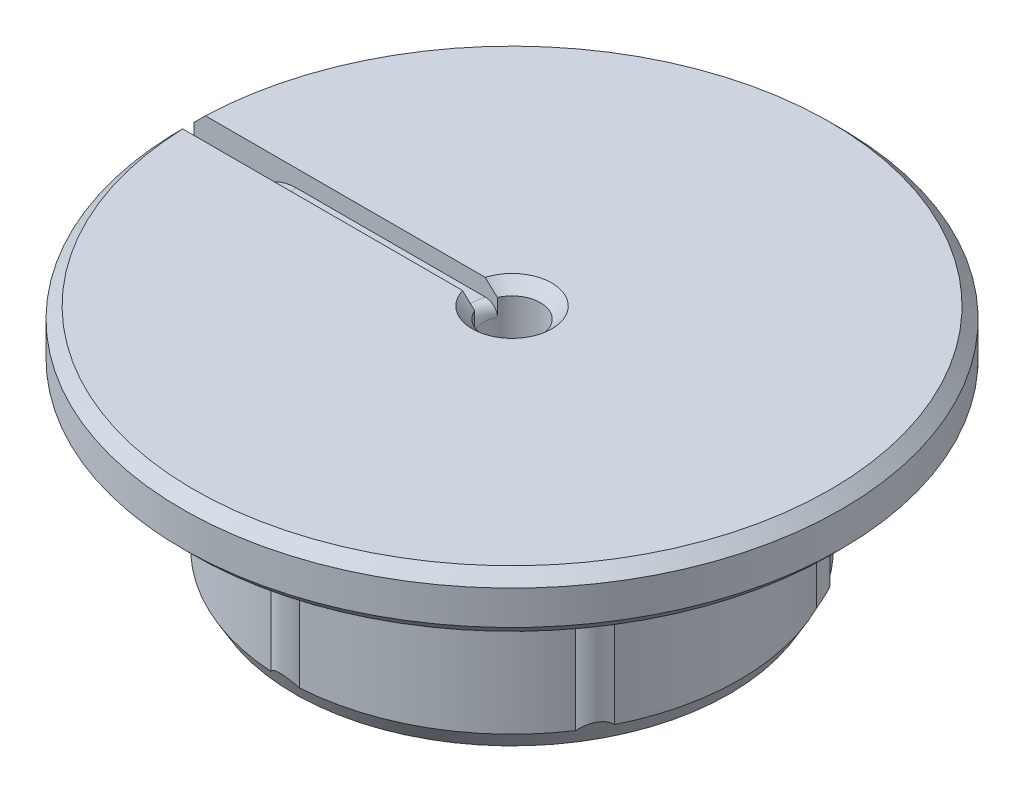
SolidWorks part; units mm, degrees
ref_plane "Front Plane" through (0, 0, 0) normal (0, 0, 1) x (1, 0, 0)
ref_plane "Top Plane" through (0, 0, 0) normal (0, 1, 0) x (1, 0, 0)
ref_plane "Right Plane" through (0, 0, 0) normal (1, 0, 0) x (0, 0, -1)
sketch "Sketch1" plane through (0, 0, 0) normal (0, 0, 1) x (1, 0, 0)
  line L0 (0, 0) -> (0, 30415.8317) construction
  line L1 (0, 0) -> (20, 0)
  line L2 (20, 0) -> (20, 15)
  line L3 (20, 15) -> (29, 15)
  line L4 (29, 15) -> (29, 20)
  line L5 (29, 20) -> (2.5, 20)
  line L6 (2.5, 20) -> (2.5, 10)
  line L7 (2.5, 10) -> (0, 10)
  line L9 (0, 10) -> (0, 0)
  dimension "D1" = 40
  dimension "D2" = 5
  dimension "D3" = 15
  dimension "D4" = 5
  dimension "D5" = 10
  dimension "D6" = 9
revolve "Revolve1" add sketch "Sketch1" angle 360 about L0
sketch "Sketch2" plane through (0, 0, 0) normal (0, -1, 0) x (1, 0, 0)
  arc A0 (-1.25, 19.9609) -> (1.25, 19.9609) centre (0, 18.4888) cw
  circle A1 centre (0, 0) radius 20 construction
  circle A2 centre (0, 0) radius 20 construction
  arc A3 (-1.25, 19.9609) -> (-16.6616, 11.063) centre (0, 0) ccw
  arc A4 (16.6616, 11.063) -> (17.9116, 8.8979) centre (16.0117, 9.2444) cw
  arc A5 (17.9116, -8.8979) -> (16.6616, -11.063) centre (16.0117, -9.2444) cw
  arc A6 (1.25, -19.9609) -> (-1.25, -19.9609) centre (0, -18.4888) cw
  arc A7 (-16.6616, -11.063) -> (-17.9116, -8.8979) centre (-16.0117, -9.2444) cw
  arc A8 (-17.9116, 8.8979) -> (-16.6616, 11.063) centre (-16.0117, 9.2444) cw
  arc A9 (-17.9116, 8.8979) -> (-17.9116, -8.8979) centre (0, 0) ccw
  arc A10 (-16.6616, -11.063) -> (-1.25, -19.9609) centre (0, 0) ccw
  arc A11 (1.25, -19.9609) -> (16.6616, -11.063) centre (0, 0) ccw
  arc A12 (17.9116, -8.8979) -> (17.9116, 8.8979) centre (0, 0) ccw
  arc A13 (16.6616, 11.063) -> (1.25, 19.9609) centre (0, 0) ccw
  point P27 (0, 0)
  dimension "D2" = 20.42
  dimension "D1" = 2.5
  dimension "D3" = 6
extrude "Boss-Extrude1" add sketch "Sketch2" against normal offset from surface (10 mm away) 5 up to face at (0, 15, -29)
sketch "Sketch3" plane through (0, 0, 0) normal (0, 0, 1) x (1, 0, 0)
  line L0 (-21, 3.2321) -> (-18.5566, -1)
  line L1 (-18.5566, -1) -> (-21, -1)
  line L2 (-21, -1) -> (-21, 3.2321)
  line L3 (-20, 0) -> (-17.9116, 0) construction
  dimension "D1" = 0.75
  dimension "D2" = 1
  dimension "D3" = 1
  dimension "D4" = 60
ref_axis "Axis1" through (0, 29.3369, 0) along (0, -1, 0)
revolve "Cut-Revolve1" cut sketch "Sketch3" angle 360 about axis through (0, 29.3369, 0) along (0, -1, 0)
chamfer "Chamfer1" distance 1 angle 45 3 edges at (0, 20, -2.5) (0, 15, -29) (0, 20, -29)
sketch "Sketch4" plane through (0, 0, 0) normal (0, -1, 0) x (1, 0, 0)
  line L0 (-23.93, 1) -> (-100, 1)
  line L1 (-100, -1) -> (-23.93, -1)
  line L2 (-100, 1) -> (-100, -1)
  line L3 (-23.93, -1) -> (-23.93, 1)
  point P5 (-100, 0)
  dimension "D1" = 2
  dimension "D2" = 100
  dimension "D3" = 23.93
extrude "Cut-Extrude1" cut sketch "Sketch4" against normal through all
sketch "Sketch5" plane through (-23.93, 0, 0) normal (-1, 0, 0) x (0, 0, 1)
  line L0 (1, 16) -> (1, 19) construction
  line L1 (-1, 20) -> (1, 20)
  line L2 (-1, 20) -> (-1, 18.5)
  line L3 (-1, 18.5) -> (1, 18.5)
  line L4 (1, 20) -> (1, 18.5)
  line L5 (1, 20) -> (1, 15) construction
  dimension "D1" = 1.5
extrude "Cut-Extrude2" cut sketch "Sketch5" against normal up to next
fillet "Fillet1" radius 4 1 edges at (-23.93, 18.5, 0)
fillet "Fillet2" radius 1 1 edges at (-2.5, 18.5, 0)
equation "\"D3@Sketch4\"=1.9in/2-0.2mm"
